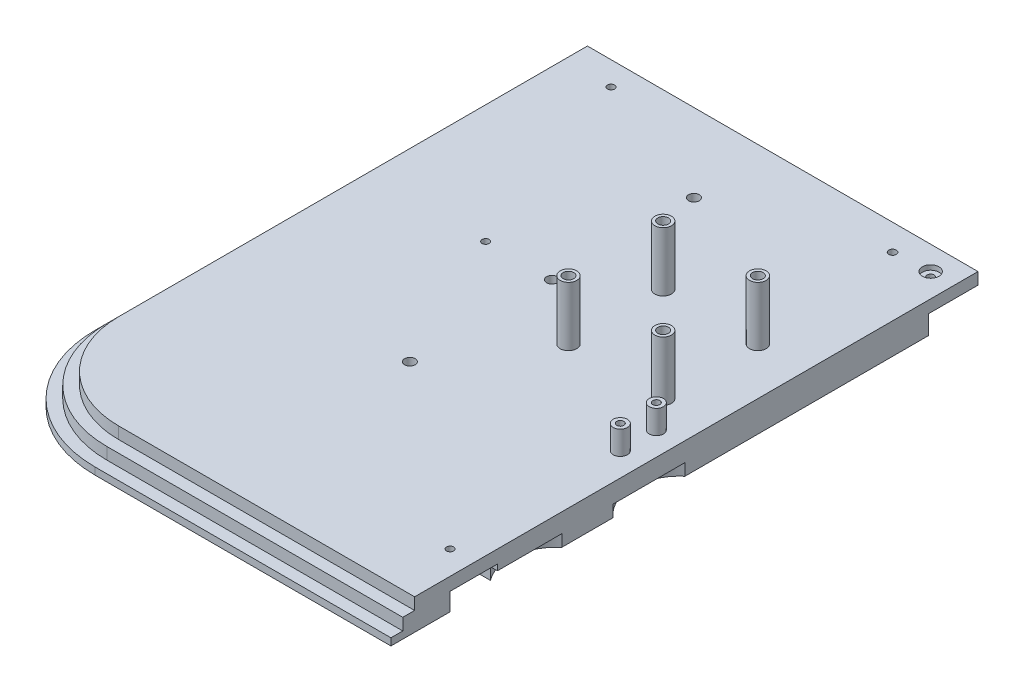
SolidWorks part; units mm, degrees
material "PETG"
ref_plane "Alzado" through (0, 0, 0) normal (0, 0, 1) x (1, 0, 0)
ref_plane "Planta" through (0, 0, 0) normal (0, 1, 0) x (1, 0, 0)
ref_plane "Vista lateral" through (0, 0, 0) normal (1, 0, 0) x (0, 0, -1)
sketch "Croquis1" plane through (0, 0, 0) normal (0, 1, 0) x (1, 0, 0)
  line L1 (125, 225) -> (-125, 225)
  line L2 (175, 175) -> (175, -175)
  line L3 (125, -225) -> (-125, -225)
  line L4 (-175, 175) -> (-175, -175)
  line L5 (175, 225) -> (-175, -225) construction
  line L6 (175, -225) -> (-175, 225) construction
  arc A0 (-125, -225) -> (-175, -175) centre (-125, -175) cw
  arc A1 (175, -175) -> (125, -225) centre (125, -175) cw
  arc A2 (125, 225) -> (175, 175) centre (125, 175) cw
  arc A3 (-125, 225) -> (-175, 175) centre (-125, 175) ccw
  point P0 (0, 0)
  dimension "D3" = 50
  dimension "D1" = 450
  dimension "D2" = 350
extrude "Saliente-Extruir1" add sketch "Croquis1" along normal blind 3
sketch "Croquis2" plane through (0, 3, 0) normal (0, 1, 0) x (1, 0, 0)
  line L8 (-125, -220) -> (125, -220)
  line L9 (170, -175) -> (170, 175)
  line L10 (125, 220) -> (-125, 220)
  line L11 (-170, 175) -> (-170, -175)
  line L12 (-125, -220) -> (125, -220)
  line L13 (170, -175) -> (170, 175)
  line L14 (125, 220) -> (-125, 220)
  line L15 (-170, 175) -> (-170, -175)
  arc A8 (-170, -175) -> (-125, -220) centre (-125, -175) ccw
  arc A9 (125, -220) -> (170, -175) centre (125, -175) ccw
  arc A10 (170, 175) -> (125, 220) centre (125, 175) ccw
  arc A11 (-125, 220) -> (-170, 175) centre (-125, 175) ccw
  arc A12 (-170, -175) -> (-125, -220) centre (-125, -175) ccw
  arc A13 (125, -220) -> (170, -175) centre (125, -175) ccw
  arc A14 (170, 175) -> (125, 220) centre (125, 175) ccw
  arc A15 (-125, 220) -> (-170, 175) centre (-125, 175) ccw
  dimension "D1" = 5
extrude "Saliente-Extruir2" add sketch "Croquis2" along normal blind 5
sketch "Croquis3" plane through (0, 8, 0) normal (0, 1, 0) x (1, 0, 0)
  line L8 (-125, -215) -> (125, -215)
  line L9 (165, -175) -> (165, 175)
  line L10 (125, 215) -> (-125, 215)
  line L11 (-165, 175) -> (-165, -175)
  line L12 (-125, -215) -> (125, -215)
  line L13 (165, -175) -> (165, 175)
  line L14 (125, 215) -> (-125, 215)
  line L15 (-165, 175) -> (-165, -175)
  arc A8 (-165, -175) -> (-125, -215) centre (-125, -175) ccw
  arc A9 (125, -215) -> (165, -175) centre (125, -175) ccw
  arc A10 (165, 175) -> (125, 215) centre (125, 175) ccw
  arc A11 (-125, 215) -> (-165, 175) centre (-125, 175) ccw
  arc A12 (-165, -175) -> (-125, -215) centre (-125, -175) ccw
  arc A13 (125, -215) -> (165, -175) centre (125, -175) ccw
  arc A14 (165, 175) -> (125, 215) centre (125, 175) ccw
  arc A15 (-125, 215) -> (-165, 175) centre (-125, 175) ccw
  dimension "D1" = 5
extrude "Saliente-Extruir3" add sketch "Croquis3" along normal blind 5
sketch "Croquis6" plane through (0, 13, 0) normal (0, 1, 0) x (1, 0, 0)
  line L0 (0, 0) -> (0, -215) construction
  line L1 (-125, -215) -> (125, -215) construction
  circle A0 centre (-87, -130) radius 2.25
  circle A1 centre (-87, -70) radius 2.25
  circle A2 centre (-87, -10) radius 2.25
  circle A3 centre (87, -130) radius 2.25
  circle A4 centre (87, -70) radius 2.25
  circle A5 centre (87, -10) radius 2.25
  dimension "D1" = 4.5
  dimension "D2" = 4.5
  dimension "D3" = 4.5
  dimension "D4" = 87
  dimension "D5" = 60
  dimension "D6" = 60
  dimension "D7" = 10
extrude "Cortar-Extruir3" cut sketch "Croquis6" against normal blind 5
sketch "Croquis7" plane through (0, 13, 0) normal (0, 1, 0) x (1, 0, 0)
  line L0 (0, -11.4875) -> (0, -220) construction
  line L1 (-125, -220) -> (125, -220) construction
  circle A0 centre (-115, -70) radius 1.5
  circle A1 centre (-115, 130) radius 1.5
  circle A2 centre (115, -70) radius 1.5
  circle A3 centre (115, 130) radius 1.5
  dimension "D1" = 3
  dimension "D2" = 3
  dimension "D3" = 115
  dimension "D4" = 70
  dimension "D5" = 130
  dimension "D6" = 115
extrude "Cortar-Extruir4" cut sketch "Croquis7" against normal through all
sketch "Croquis8" plane through (0, 13, 0) normal (0, 1, 0) x (1, 0, 0)
  line L0 (13.0147, -158) -> (13.0147, -178) construction
  line L4 (16.0147, -158) -> (16.0147, -178)
  line L5 (10.0147, -158) -> (10.0147, -178)
  line L6 (25.0147, -158) -> (25.0147, -178) construction
  line L7 (28.0147, -158) -> (28.0147, -178)
  line L8 (22.0147, -158) -> (22.0147, -178)
  line L9 (25.0147, -106) -> (25.0147, -126) construction
  line L10 (28.0147, -106) -> (28.0147, -126)
  line L11 (22.0147, -106) -> (22.0147, -126)
  line L12 (13.0147, -106) -> (13.0147, -126) construction
  line L15 (16.0147, -106) -> (16.0147, -126)
  line L16 (10.0147, -106) -> (10.0147, -126)
  arc A0 (10.0147, -168) -> (13.0147, -171) centre (13.0147, -168) ccw construction
  arc A1 (25.0147, -171) -> (28.0147, -168) centre (25.0147, -168) ccw construction
  arc A2 (16.0147, -116) -> (13.0147, -113) centre (13.0147, -116) ccw construction
  arc A3 (22.0147, -116) -> (25.0147, -119) centre (25.0147, -116) ccw construction
  arc A6 (16.0147, -158) -> (10.0147, -158) centre (13.0147, -158) ccw
  arc A7 (10.0147, -178) -> (16.0147, -178) centre (13.0147, -178) ccw
  arc A8 (28.0147, -158) -> (22.0147, -158) centre (25.0147, -158) ccw
  arc A9 (22.0147, -178) -> (28.0147, -178) centre (25.0147, -178) ccw
  arc A10 (28.0147, -106) -> (22.0147, -106) centre (25.0147, -106) ccw
  arc A11 (22.0147, -126) -> (28.0147, -126) centre (25.0147, -126) ccw
  arc A14 (16.0147, -106) -> (10.0147, -106) centre (13.0147, -106) ccw
  arc A15 (10.0147, -126) -> (16.0147, -126) centre (13.0147, -126) ccw
  arc A16 (13.0147, -113) -> (10.0147, -116) centre (13.0147, -116) ccw construction
  arc A17 (10.0147, -116) -> (13.0147, -119) centre (13.0147, -116) ccw construction
  arc A18 (13.0147, -119) -> (16.0147, -116) centre (13.0147, -116) ccw construction
  arc A19 (28.0147, -116) -> (25.0147, -113) centre (25.0147, -116) ccw construction
  arc A20 (25.0147, -119) -> (28.0147, -116) centre (25.0147, -116) ccw construction
  arc A21 (25.0147, -113) -> (22.0147, -116) centre (25.0147, -116) ccw construction
  arc A22 (25.0147, -165) -> (22.0147, -168) centre (25.0147, -168) ccw construction
  arc A23 (22.0147, -168) -> (25.0147, -171) centre (25.0147, -168) ccw construction
  arc A24 (28.0147, -168) -> (25.0147, -165) centre (25.0147, -168) ccw construction
  arc A25 (16.0147, -168) -> (13.0147, -165) centre (13.0147, -168) ccw construction
  arc A26 (13.0147, -171) -> (16.0147, -168) centre (13.0147, -168) ccw construction
  arc A27 (13.0147, -165) -> (10.0147, -168) centre (13.0147, -168) ccw construction
  point P10 (13.0147, -168)
  point P16 (25.0147, -168)
  point P23 (25.0147, -116)
  point P32 (13.0147, -116)
  dimension "D1" = 6
  dimension "D2" = 6
  dimension "D3" = 6
  dimension "D4" = 6
  dimension "D5" = 12
  dimension "D6" = 52
  dimension "D7" = 116
  dimension "D8" = 13.0147
  dimension "D9" = 20
  dimension "D10" = 20
  dimension "D11" = 20
  dimension "D12" = 20
extrude "Cortar-Extruir5" cut sketch "Croquis8" against normal blind 8
sketch "Croquis9" plane through (0, 13, 0) normal (0, 1, 0) x (1, 0, 0)
  circle A0 centre (13.0147, -168) radius 1.5
  circle A1 centre (25.0147, -168) radius 1.5
  circle A2 centre (13.0147, -116) radius 1.5
  circle A3 centre (25.0147, -116) radius 1.5
  circle A4 centre (-87, -70) radius 2.25 construction
  circle A5 centre (-87, -130) radius 1.5
  circle A6 centre (-87, -70) radius 1.5
  circle A7 centre (-87, -10) radius 1.5
  circle A8 centre (87, -10) radius 1.5
  circle A9 centre (87, -70) radius 1.5
  circle A10 centre (87, -130) radius 1.5
  dimension "D1" = 3
  dimension "D2" = 3
  dimension "D3" = 3
  dimension "D4" = 3
  dimension "D5" = 100.0147
  dimension "D6" = 112.0147
  dimension "D7" = 46
  dimension "D8" = 98
extrude "Cortar-Extruir6" cut sketch "Croquis9" against normal through all
sketch "Croquis10" plane through (0, 13, 0) normal (0, 1, 0) x (1, 0, 0)
  line L1 (50, -120) -> (75, -120)
  line L2 (50, -120) -> (50, -170)
  line L3 (50, -170) -> (75, -170)
  line L4 (75, -120) -> (75, -170)
  dimension "D1" = 50
  dimension "D2" = 25
  dimension "D3" = 120
  dimension "D4" = 50
extrude "Cortar-Extruir7" cut sketch "Croquis10" against normal blind 5
chamfer "Chaflán1" distance 5 angle 45 4 edges at (62.5, 13, 120) (50, 13, 145) (62.5, 13, 170) (75, 13, 145)
sketch "Croquis13" plane through (0, 13, 0) normal (0, 1, 0) x (1, 0, 0)
  circle A0 centre (-60, -50) radius 2.25
  circle A1 centre (-20, -50) radius 2.25
  circle A2 centre (-20, -90) radius 2.25
  circle A3 centre (-60, -90) radius 2.25
  circle A4 centre (-20, -50) radius 3.5
  circle A5 centre (-60, -50) radius 3.5
  circle A6 centre (-60, -90) radius 3.5
  circle A7 centre (-20, -90) radius 3.5
  dimension "D1" = 4.5
  dimension "D2" = 40
  dimension "D6" = 7
  dimension "D3" = 40
  dimension "D4" = 20
  dimension "D5" = 50
extrude "Saliente-Extruir4" add sketch "Croquis13" along normal blind 25
sketch "Croquis14" plane through (0, 13, 0) normal (0, 1, 0) x (1, 0, 0)
  circle A0 centre (3.15, -40) radius 1.25
  circle A1 centre (67.55, -40) radius 1.25
  circle A3 centre (67.55, -40) radius 3
  circle A4 centre (3.15, -40) radius 3
  circle A5 centre (3, -91.9) radius 3
  circle A6 centre (3, -91.9) radius 1.25
  circle A7 centre (67.4, -91.9) radius 3
  circle A8 centre (67.4, -91.9) radius 1.25
  circle A9 centre (-10, -102.9) radius 1.5
  circle A10 centre (-10, -102.9) radius 3
  circle A11 centre (-10, -118.1085) radius 3
  circle A12 centre (-10, -118.1085) radius 1.5
  dimension "D1" = 2.5
  dimension "D2" = 6
  dimension "D7" = 3
  dimension "D8" = 6
  dimension "D9" = 6
  dimension "D10" = 3
  dimension "D3" = 51.9
  dimension "D4" = 64.4
  dimension "D5" = 40
  dimension "D6" = 3
  dimension "D11" = 11
  dimension "D12" = 13
  dimension "D13" = 15.2085
  dimension "D14" = 64.4
  dimension "D15" = 0.15
extrude "Saliente-Extruir5" add sketch "Croquis14" along normal blind 10
sketch "Croquis12" plane through (0, 13, 0) normal (0, 1, 0) x (1, 0, 0)
  line L0 (-25.1, 12) -> (-25.1, 13.6) construction
  line L1 (-25.1, 12) -> (-23.5, 12) construction
  line L2 (25.1, 12) -> (23.5, 12) construction
  line L3 (25.1, 12) -> (25.1, 13.6) construction
  line L4 (25.1, 162.2) -> (25.1, 160.6) construction
  line L5 (25.1, 162.2) -> (23.5, 162.2) construction
  line L6 (-25.1, 162.2) -> (-23.5, 162.2) construction
  line L7 (-25.1, 162.2) -> (-25.1, 160.6) construction
  circle A0 centre (-25.1, 162.2) radius 1.6
  circle A1 centre (25.1, 162.2) radius 1.6
  circle A2 centre (-25.1, 12) radius 1.6
  circle A3 centre (25.1, 12) radius 1.6
  dimension "D4" = 3.2
  dimension "D1" = 12
  dimension "D2" = 47
  dimension "D3" = 23.5
  dimension "D5" = 147
  dimension "D6" = 147
extrude "Cortar-Extruir9" cut sketch "Croquis12" against normal through all
sketch "Croquis11" plane through (0, 0, 0) normal (0, -1, 0) x (1, 0, 0)
  line L0 (13.0147, 168) -> (25.0147, 168) construction
  line L1 (13.0147, 188) -> (25.0147, 188)
  line L2 (13.0147, 148) -> (25.0147, 148)
  line L3 (13.0147, 116) -> (25.0147, 116) construction
  line L4 (13.0147, 136) -> (25.0147, 136)
  line L5 (13.0147, 96) -> (25.0147, 96)
  circle A4 centre (87, 130) radius 6
  circle A5 centre (87, 70) radius 6
  circle A6 centre (87, 10) radius 6
  circle A7 centre (-87, 10) radius 6
  circle A8 centre (-87, 70) radius 6
  circle A9 centre (-87, 130) radius 6
  circle A10 centre (-115, 70) radius 6
  circle A11 centre (115, 70) radius 6
  circle A12 centre (115, -130) radius 6
  circle A15 centre (-115, -130) radius 6
  arc A16 (13.0147, 188) -> (13.0147, 148) centre (13.0147, 168) ccw
  arc A17 (25.0147, 148) -> (25.0147, 188) centre (25.0147, 168) ccw
  circle A18 centre (-25.1, -162.2) radius 6
  arc A19 (13.0147, 136) -> (13.0147, 96) centre (13.0147, 116) ccw
  arc A20 (25.0147, 96) -> (25.0147, 136) centre (25.0147, 116) ccw
  circle A21 centre (25.1, -162.2) radius 6
  circle A22 centre (-25.1, -12) radius 6
  circle A23 centre (25.1, -12) radius 6
  point P3 (19.0147, 168)
  point P10 (19.0147, 116)
  dimension "D1" = 12
  dimension "D2" = 20
  dimension "D3" = 20
extrude "Cortar-Extruir8" cut sketch "Croquis11" against normal blind 5
sketch "Croquis16" plane through (0, 0, 0) normal (1, 0, 0) x (0, 0, -1)
  line L5 (-175, 8) -> (175, 8) construction
  line L6 (2, 8) -> (42, 8)
  line L7 (2, 8) -> (2, 0)
  line L8 (2, 0) -> (42, 0)
  line L9 (42, 8) -> (42, 0)
  line L11 (-175, 0) -> (175, 0) construction
  point P6 (5.7805, 0)
  dimension "D1" = 40
  dimension "D2" = 2
extrude "Cortar-Extruir10" cut sketch "Croquis16" against normal mid plane 40
sketch "Croquis17" plane through (0, 13, 0) normal (0, 1, 0) x (1, 0, 0)
  line L0 (-175, 23) -> (0, 23)
  line L2 (0, 23) -> (0, -225)
  line L3 (-125, -225) -> (125, -225) construction
  line L4 (-175, 175) -> (-175, -175) construction
  line L5 (-175, 23) -> (-175, 225)
  line L6 (-175, 225) -> (175, 225)
  line L7 (175, 225) -> (175, -225)
  line L8 (175, -225) -> (0, -225)
  line L9 (125, 225) -> (-125, 225) construction
  line L10 (175, -175) -> (175, 175) construction
  point P3 (0, 41.0843)
  point P17 (0, 50)
  dimension "D1" = 248
extrude "Cortar-Extruir11" cut sketch "Croquis17" against normal mid plane 40
sketch "Croquis19" plane through (0, 13, 0) normal (0, 1, 0) x (1, 0, 0)
  line L0 (-175, 23) -> (-175, -175) construction
  line L1 (-165, 23) -> (0, 23) construction
  line L2 (-125, -225) -> (0, -225) construction
  line L3 (0, 23) -> (0, -215) construction
  circle A0 centre (-145, 13) radius 1.5
  circle A1 centre (-10, -190) radius 1.5
  circle A2 centre (-10, 13) radius 1.5
  dimension "D1" = 3
  dimension "D2" = 3
  dimension "D3" = 3
  dimension "D5" = 30
  dimension "D6" = 10
  dimension "D7" = 35
  dimension "D8" = 10
  dimension "D9" = 10
extrude "Cortar-Extruir12" cut sketch "Croquis19" against normal blind 70
sketch "Croquis20" plane through (0, 0, 0) normal (1, 0, 0) x (0, 0, -1)
  line L0 (-225, 0) -> (-183.1861, 0) construction
  line L1 (-200, 0) -> (-180, 0)
  line L2 (-200, 0) -> (-200, 7.5)
  line L3 (-200, 7.5) -> (-180, 7.5)
  line L4 (-180, 0) -> (-180, 7.5)
  line L5 (-225, 0) -> (-225, 3) construction
  dimension "D1" = 7.5
  dimension "D2" = 25
  dimension "D3" = 20
extrude "Cortar-Extruir13" cut sketch "Croquis20" against normal blind 20
sketch "Croquis21" plane through (0, 0, -23) normal (0, 0, -1) x (-1, 0, 0)
  line L0 (175, 0) -> (175, 3) construction
  line L1 (135, 7.5) -> (155, 7.5)
  line L2 (135, 7.5) -> (135, 0)
  line L3 (135, 0) -> (155, 0)
  line L4 (155, 7.5) -> (155, 0)
  line L5 (20, 0) -> (175, 0) construction
  dimension "D1" = 20
  dimension "D2" = 20
  dimension "D3" = 7.5
extrude "Cortar-Extruir14" cut sketch "Croquis21" against normal blind 20
sketch "Croquis23" plane through (0, 13, 0) normal (0, 1, 0) x (1, 0, 0)
  circle A3 centre (-10, 13) radius 3.5
  circle A4 centre (-10, 13) radius 3.5
  dimension "D1" = 2
extrude "Cortar-Extruir16" cut sketch "Croquis23" against normal blind 2
sketch "Croquis22" plane through (0, 0, 0) normal (0, -1, 0) x (1, 0, 0)
  line L0 (-27, 3.8868) -> (-27, 5)
  line L2 (-94.2801, -16) -> (-79.7199, -16) construction
  line L3 (-79.7199, -16) -> (-40.5919, -16)
  line L22 (-27, 5) -> (-7, 5)
  line L23 (-27, 5) -> (-7, 5)
  line L25 (-27, 0.8604) -> (-27, 5)
  line L32 (-128, 4) -> (-128, -16)
  line L33 (-128, -16) -> (-37.4693, -16)
  line L36 (-7, 5) -> (-7, 97.8778)
  line L37 (-7, 134.1222) -> (-7, 149.8778)
  line L38 (-13.5183, 173) -> (-27, 173)
  line L39 (-27, 173) -> (-27, 207)
  line L40 (-27, 207) -> (-7, 207)
  line L41 (-7, 207) -> (-7, 218)
  line L42 (-7, 218) -> (-125, 218)
  line L43 (-168, 175) -> (-168, -16)
  line L44 (-168, -16) -> (-162, -16)
  line L45 (-162, -16) -> (-162, 4)
  line L46 (-162, 4) -> (-128, 4)
  line L47 (-128, 4) -> (-128, -16)
  line L48 (-128, -16) -> (-94.2801, -16)
  line L51 (-7, 5) -> (-7, 97.8778)
  line L52 (-7, 134.1222) -> (-7, 149.8778)
  line L54 (-27, 173) -> (-27, 207)
  line L55 (-27, 207) -> (-7, 207)
  line L56 (-7, 207) -> (-7, 218)
  line L57 (-7, 218) -> (-125, 218)
  line L58 (-168, 175) -> (-168, -16)
  line L59 (-168, -16) -> (-162, -16)
  line L60 (-162, -16) -> (-162, 4)
  line L61 (-162, 4) -> (-128, 4)
  line L63 (-13.5183, 173) -> (-27, 173)
  arc A1 (-94.2801, -16) -> (-79.7199, -16) centre (-87, 10) ccw construction
  arc A3 (-11.5, -3.5715) -> (-11.5, -20.4285) centre (-25.1, -12) ccw
  arc A4 (-27, 3.8868) -> (-40.5919, -16) centre (-25.1, -12) ccw
  circle A5 centre (-87, 130) radius 26
  arc A6 (-7, 134.1222) -> (-7, 97.8778) centre (13.0147, 116) ccw
  arc A7 (-13.5183, 173) -> (-7, 149.8778) centre (13.0147, 168) ccw
  arc A8 (-125, 218) -> (-168, 175) centre (-125, 175) ccw
  arc A9 (-7, 134.1222) -> (-7, 97.8778) centre (13.0147, 116) ccw
  arc A10 (-13.5183, 173) -> (-7, 149.8778) centre (13.0147, 168) ccw
  arc A11 (-125, 218) -> (-168, 175) centre (-125, 175) ccw
  circle A12 centre (-87, 130) radius 26
  circle A14 centre (-115, 70) radius 16
  arc A15 (-108.5, 84.6202) -> (-108.5, 55.3798) centre (-115, 70) ccw
  circle A17 centre (-87, 70) radius 26
  arc A18 (-108.5, 55.3798) -> (-108.5, 84.6202) centre (-87, 70) ccw
  arc A19 (-108.5, 84.6202) -> (-108.5, 55.3798) centre (-87, 70) ccw construction
  circle A20 centre (-87, 10) radius 27
  arc A21 (-79.7199, -16) -> (-94.2801, -16) centre (-87, 10) ccw
  arc A22 (-108.5, 55.3798) -> (-108.5, 84.6202) centre (-115, 70) ccw construction
  arc A32 (-27, 0.8604) -> (-37.4693, -16) centre (-25.1, -12) ccw
  point P3 (-40.5919, -16.6064)
  dimension "D1" = 7
  dimension "D2" = 20
  dimension "D3" = 10
  dimension "D4" = 20
  dimension "D5" = 21
  dimension "D6" = 10
extrude "Cortar-Extruir17" cut sketch "Croquis22" against normal blind 6 contours A21 L48 L47 L61 L60 L59 L58 A11 L57 L56 L55 L54 L63 A10 L52 A9 L51 L23 L0 A4 L3 | A15 A18 | A12
